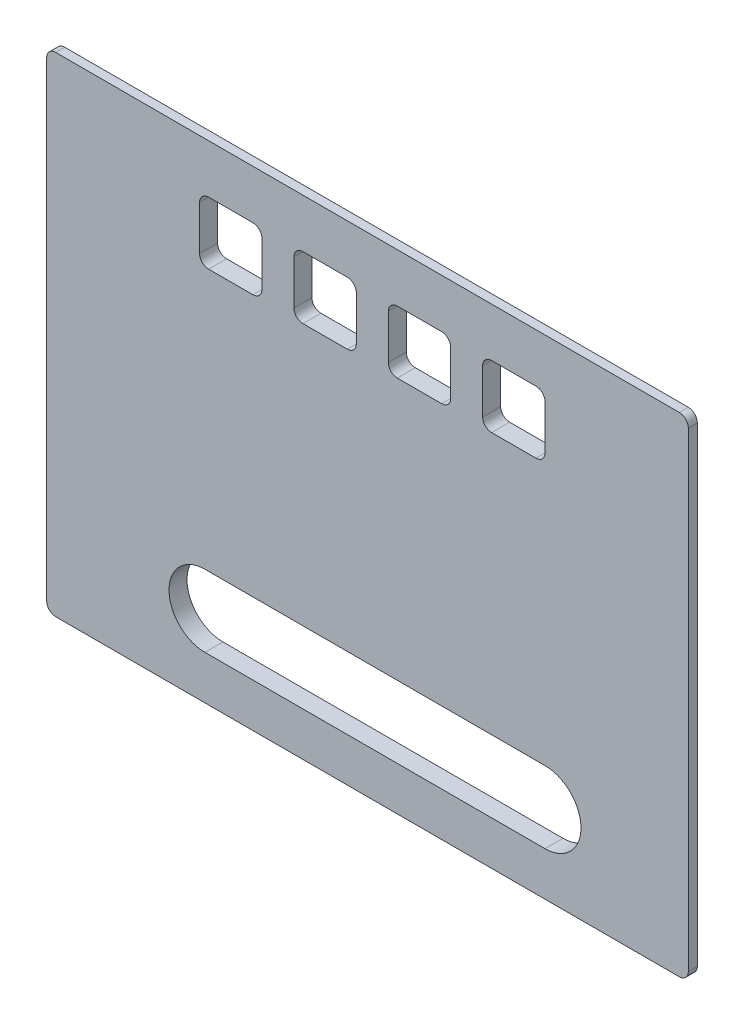
SolidWorks part; units mm, degrees
ref_plane "Спереди" through (0, 0, 0) normal (0, 0, 1) x (1, 0, 0)
ref_plane "Сверху" through (0, 0, 0) normal (0, 1, 0) x (1, 0, 0)
ref_plane "Справа" through (0, 0, 0) normal (1, 0, 0) x (0, 0, -1)
other "Configuration Table"
sketch "Эскиз1" plane through (0, 0, 0) normal (0, 0, 1) x (1, 0, 0)
  line L1 (3, 3) -> (104, 3)
  line L2 (3, 3) -> (3, 77)
  line L3 (3, 77) -> (104, 77)
  line L4 (104, 3) -> (104, 77)
extrude "Бобышка-Вытянуть1" add sketch "Эскиз1" along normal blind 3
sketch "Эскиз2" plane through (0, 0, 0) normal (0, 0, 1) x (1, 0, 0)
  line L1 (0, 0) -> (107, 0)
  line L2 (0, 0) -> (0, 80)
  line L3 (0, 80) -> (107, 80)
  line L4 (107, 0) -> (107, 80)
extrude "Бобышка-Вытянуть2" add sketch "Эскиз2" along normal blind 1.5 from offset 1.5
sketch "Эскиз3" plane through (0, 0, 3) normal (0, 0, 1) x (1, 0, 0)
  line L0 (26.4, 13.3) -> (83.1, 13.3) construction
  line L1 (25.5, 62.95) -> (35.9, 62.95)
  line L2 (25.5, 62.95) -> (25.5, 73.35)
  line L3 (25.5, 73.35) -> (35.9, 73.35)
  line L4 (35.9, 62.95) -> (35.9, 73.35)
  line L5 (41.233, 62.95) -> (51.633, 62.95)
  line L6 (41.233, 62.95) -> (41.233, 73.35)
  line L7 (41.233, 73.35) -> (51.633, 73.35)
  line L8 (51.633, 62.95) -> (51.633, 73.35)
  line L9 (56.967, 62.95) -> (67.367, 62.95)
  line L10 (56.967, 62.95) -> (56.967, 73.35)
  line L11 (56.967, 73.35) -> (67.367, 73.35)
  line L12 (67.367, 62.95) -> (67.367, 73.35)
  line L13 (72.7, 62.95) -> (83.1, 62.95)
  line L14 (72.7, 62.95) -> (72.7, 73.35)
  line L15 (72.7, 73.35) -> (83.1, 73.35)
  line L16 (83.1, 62.95) -> (83.1, 73.35)
  line L17 (26.4, 19.3) -> (83.1, 19.3)
  line L18 (26.4, 7.3) -> (83.1, 7.3)
  arc A0 (26.4, 19.3) -> (26.4, 7.3) centre (26.4, 13.3) ccw
  arc A1 (83.1, 7.3) -> (83.1, 19.3) centre (83.1, 13.3) ccw
  point P18 (54.75, 13.3)
extrude "Вырез-Вытянуть1" cut sketch "Эскиз3" against normal blind 5
sketch "Эскиз4" plane through (0, 0, 0) normal (0, 0, 1) x (1, 0, 0)
  line L1 (3, 77) -> (104, 77)
  line L2 (3, 77) -> (3, 78.5)
  line L3 (3, 78.5) -> (104, 78.5)
  line L4 (104, 77) -> (104, 78.5)
extrude "top_rear_inner_extension_1p5mm" add sketch "Эскиз4" along normal blind 3
sketch "Эскиз5" plane through (0, 0, 0) normal (0, 0, 1) x (1, 0, 0)
  line L1 (0, 80) -> (107, 80)
  line L2 (0, 80) -> (0, 81.5)
  line L3 (0, 81.5) -> (107, 81.5)
  line L4 (107, 80) -> (107, 81.5)
extrude "top_rear_outer_skin_extension_1p5mm" add sketch "Эскиз5" along normal blind 1.5 from offset 1.5
fillet "tool_D3_R1p5_button_corners" radius 1.5 16 edges at (72.7, 73.35, 1.5) (83.1, 73.35, 1.5) (83.1, 62.95, 1.5) (72.7, 62.95, 1.5) (56.967, 73.35, 1.5) (67.367, 73.35, 1.5) (67.367, 62.95, 1.5) (56.967, 62.95, 1.5) (41.233, 73.35, 1.5) (51.633, 73.35, 1.5) (51.633, 62.95, 1.5) (41.233, 62.95, 1.5) (25.5, 62.95, 1.5) (35.9, 62.95, 1.5) (35.9, 73.35, 1.5) (25.5, 73.35, 1.5) tangent propagation no
fillet "tool_D3_R1p5_top_outer_contour" radius 1.5 4 edges at (0, 81.5, 2.25) (107, 81.5, 2.25) (107, 0, 2.25) (0, 0, 2.25)
